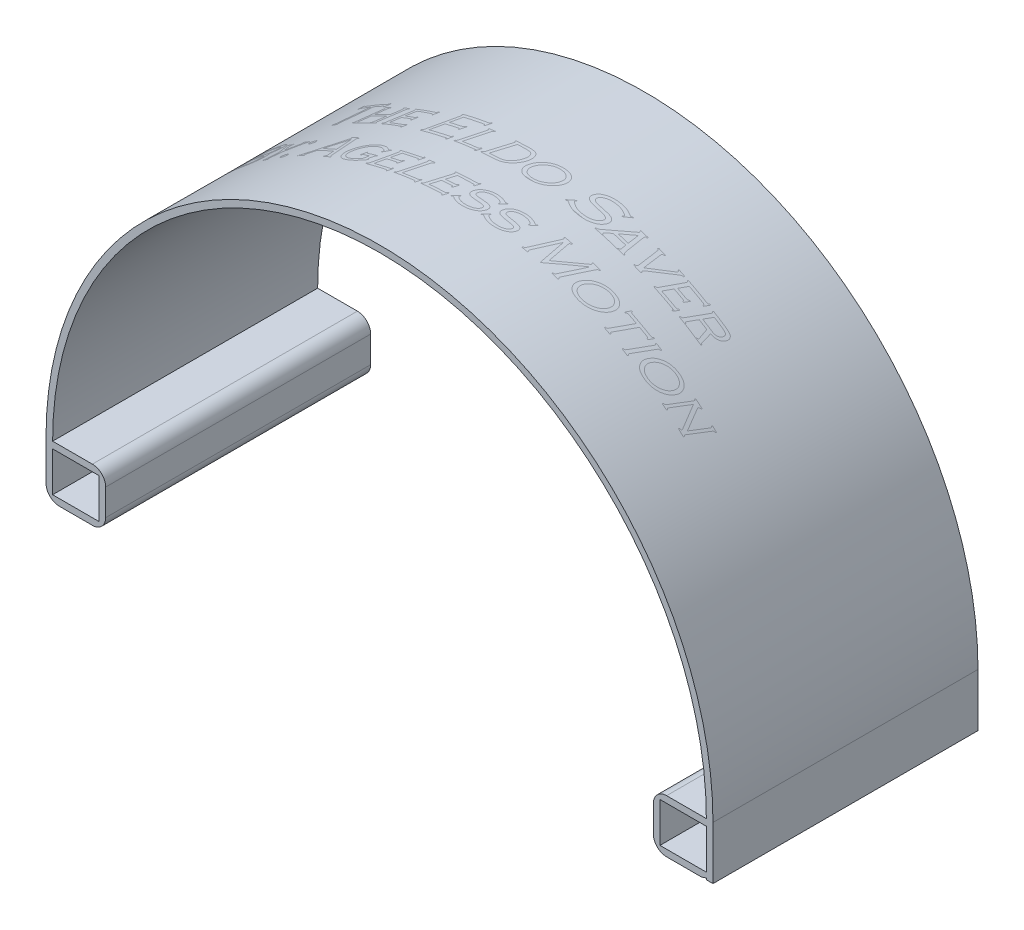
SolidWorks part; units mm, degrees
material "Nylon 6/10"
ref_plane "Front Plane" through (0, 0, 0) normal (0, 0, 1) x (1, 0, 0)
ref_plane "Top Plane" through (0, 0, 0) normal (0, 1, 0) x (1, 0, 0)
ref_plane "Right Plane" through (0, 0, 0) normal (1, 0, 0) x (0, 0, -1)
sketch "Sketch1" plane through (0, 0, 0) normal (0, 0, 1) x (1, 0, 0)
  line L0 (-74, 0) -> (74, 0) construction
  line L1 (-74, 0) -> (-75.5, 0)
  line L2 (74, 0) -> (75.5, 0)
  arc A0 (74, 0) -> (-74, 0) centre (0, 0) ccw
  arc A1 (75.5, 0) -> (-75.5, 0) centre (0, 0) ccw
  dimension "D1" = 74
  dimension "D2" = 1.5
extrude "Boss-Extrude2" add sketch "Sketch1" along normal mid plane 60
ref_plane "Plane1" through (0, 150, 0) normal (0, 1, 0) x (1, 0, 0)
sketch "Sketch3" plane through (0, 150, 0) normal (0, 1, 0) x (1, 0, 0)
  line L0 (-115.5974, 0) -> (115.5974, 0)
  text T0 "<i>The Eldo Saver</i>\r\n<i>By: Ageless Motion</i>" font "Copperplate Gothic Light" height in points 36
  point P4 (0, 0)
wrap "Wrap1" sketch "Sketch3" wrap type scribe source sketch "Sketch3" face at (0, 37.75, 0)
sketch "Sketch4" plane through (0, 0, 0) normal (0, -1, 0) x (1, 0, 0)
  line L1 (-75.5, 30) -> (-74, 30)
  line L2 (-75.5, 30) -> (-75.5, -30)
  line L3 (-75.5, -30) -> (-74, -30)
  line L4 (-74, 30) -> (-74, -30)
  line L5 (74, 30) -> (75.5, 30)
  line L6 (74, 30) -> (74, -30)
  line L7 (74, -30) -> (75.5, -30)
  line L8 (75.5, 30) -> (75.5, -30)
extrude "Boss-Extrude3" add sketch "Sketch4" along normal blind 12
sketch "Sketch5" plane through (74, 0, 0) normal (-1, 0, 0) x (0, 0, 1)
  line L0 (30, -12) -> (30, 0) construction
  line L1 (-30, -12) -> (30, -12)
  line L2 (-30, -12) -> (-30, -10.5)
  line L3 (-30, -10.5) -> (30, -10.5)
  line L4 (30, -12) -> (30, -10.5)
  dimension "D1" = 1.5
extrude "Boss-Extrude4" add sketch "Sketch5" along normal blind 12
sketch "Sketch6" plane through (0, -10.5, 0) normal (0, 1, 0) x (1, 0, 0)
  line L0 (-75.5, -30) -> (75.5, -30) construction
  line L1 (62, 30) -> (63.5, 30)
  line L2 (62, 30) -> (62, -30)
  line L3 (62, -30) -> (63.5, -30)
  line L4 (63.5, 30) -> (63.5, -30)
  dimension "D1" = 1.5
extrude "Boss-Extrude5" add sketch "Sketch6" along normal blind 10.5
sketch "Sketch9" plane through (63.5, 0, 0) normal (1, 0, 0) x (0, 0, -1)
  line L0 (30, -12) -> (30, 0) construction
  line L1 (-30, 0) -> (30, 0)
  line L2 (-30, 0) -> (-30, -1.5)
  line L3 (-30, -1.5) -> (30, -1.5)
  line L4 (30, 0) -> (30, -1.5)
  dimension "D1" = 1.5
extrude "Boss-Extrude6" add sketch "Sketch9" along normal up to next
fillet "Fillet1" radius 3 3 edges at (62, -12, 0) (75.5, -12, 0) (62, 0, 0)
mirror "Mirror11" about plane through (0, 0, 0) normal (1, 0, 0) of "Boss-Extrude3", "Boss-Extrude4", "Boss-Extrude5", "Boss-Extrude6"
fillet "Fillet3" radius 3 3 edges at (-75.5, -12, 0) (-62, -12, 0) (-62, 0, 0)
equation "\"userHeight\"= 1700mm"
equation "\"velcro_inner_radius\"= IIF ( \"userHeight\" > 1850 , 92 , 74 )'velcro inner radius"
equation "\"D1@Sketch1\"=\"velcro_inner_radius\""
